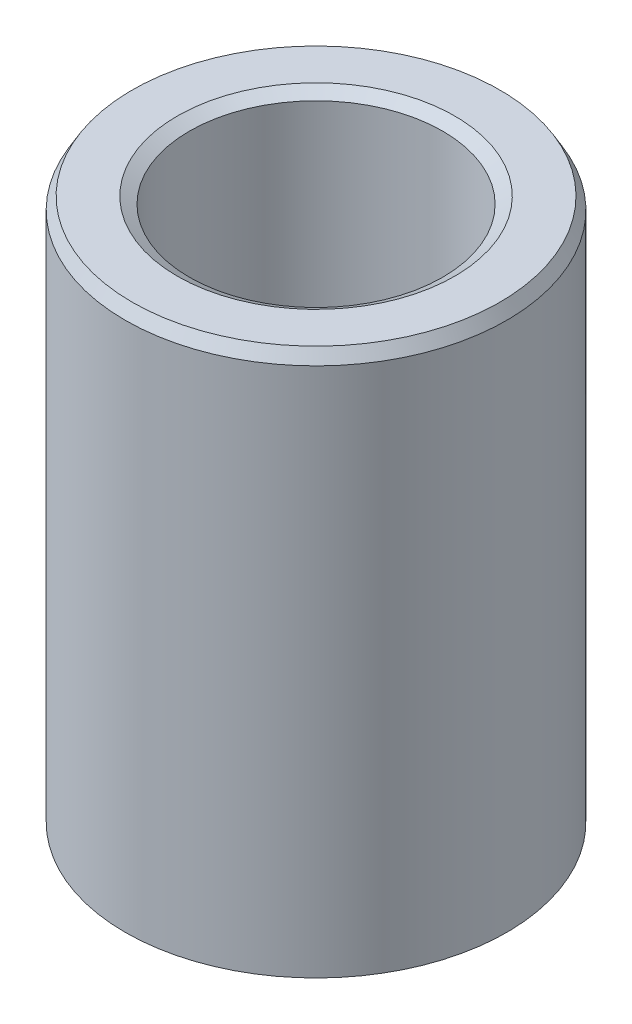
SolidWorks part; units mm, degrees
ref_plane "Front Plane" through (0, 0, 0) normal (0, 0, 1) x (1, 0, 0)
ref_plane "Top Plane" through (0, 0, 0) normal (0, 1, 0) x (1, 0, 0)
ref_plane "Right Plane" through (0, 0, 0) normal (1, 0, 0) x (0, 0, -1)
sketch "Sketch1" plane through (0, 0, 0) normal (0, 1, 0) x (1, 0, 0)
  circle A0 centre (0, 0) radius 32.5
  dimension "SLEEVE_OD" = 65
extrude "Boss-Extrude1" add sketch "Sketch1" along normal blind 93.5357
sketch "Sketch2" plane through (0, 0, 0) normal (0, 1, 0) x (1, 0, 0)
  circle A0 centre (0, 0) radius 21.5661
  dimension "BORE_D" = 43.1321
extrude "Cut-Extrude1" cut sketch "Sketch2" along normal through all
chamfer "Chamfer1" distance 2.0664 angle 30 4 edges at (0, 93.5357, 21.5661) (0, 0, 21.5661) (0, 0, 32.5) (0, 93.5357, 32.5) first distance on face at (0, 93.5357, 21.5661) first distance on face at (0, 0, 21.5661) first distance on face at (0, 93.5357, 32.5)
